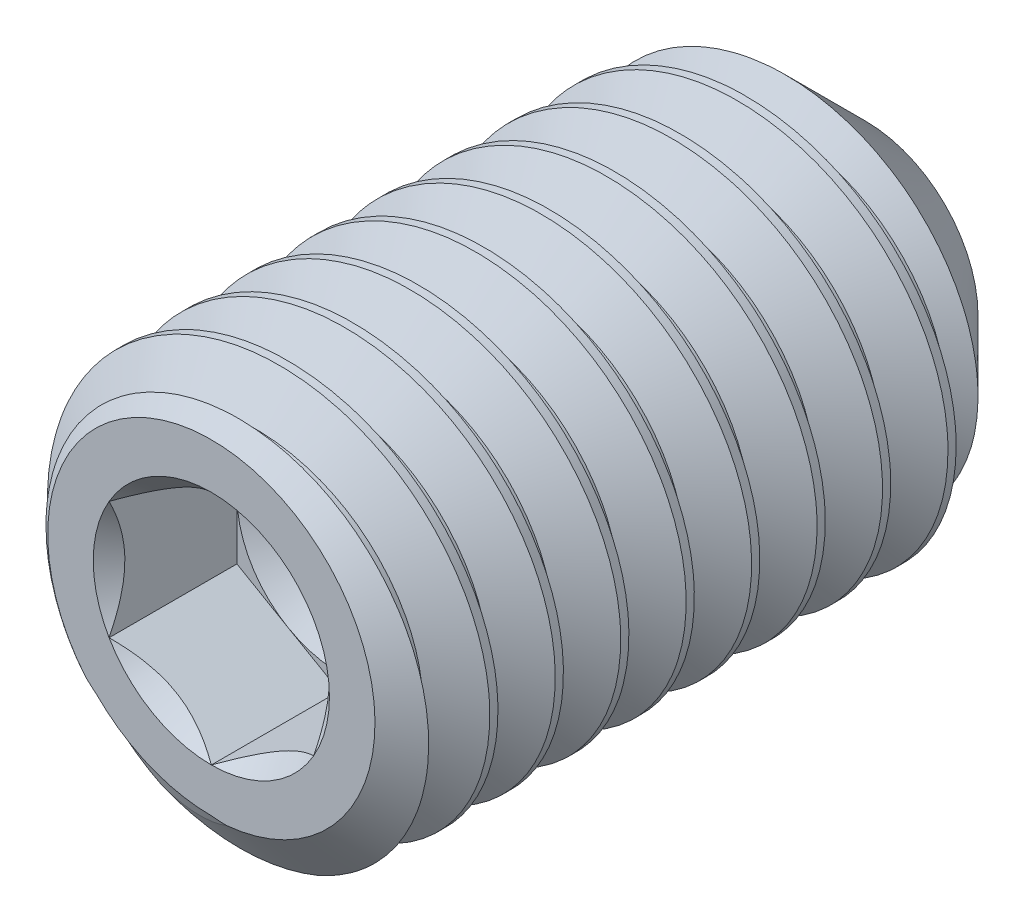
SolidWorks part; units mm, degrees
ref_plane "Front" through (0, 0, 0) normal (0, 0, 1) x (1, 0, 0)
ref_plane "Top" through (0, 0, 0) normal (0, 1, 0) x (1, 0, 0)
ref_plane "Right" through (0, 0, 0) normal (1, 0, 0) x (0, 0, -1)
sketch "Sketch22" plane through (0, 0, 0) normal (1, 0, 0) x (0, 0, -1)
  line L0 (-3.5884, 0) -> (-3.5884, 2)
  line L1 (-3.5884, 2) -> (-3.2383, 2.5)
  line L2 (-3.2383, 2.5) -> (3.2815, 2.5)
  line L3 (3.2815, 2.5) -> (4.4116, 1.3699)
  line L4 (4.4116, 1.3699) -> (3.5884, 0)
  line L5 (3.5884, 0) -> (-3.5884, 0)
  line L6 (3.5884, 0) -> (4.4116, 0) construction
  line L7 (4.4116, 0) -> (4.4116, 1.3699) construction
  line L8 (4.4116, -1.3699) -> (3.5884, 0) construction
  line L9 (-3.2383, -2.5) -> (3.2815, -2.5) construction
  dimension "Dia" = 5
  dimension "Length" = 8
  dimension "D3" = 35
  dimension "D5" = 118
  dimension "D6" = 45
  dimension "D7" = 4
revolve "Revolve1" add sketch "Sketch22" angle 360 about L6
ref_plane "Plane1" through (0, 0, -4.4116) normal (0, 0, 1) x (1, 0, 0)
sketch "Sketch27" plane through (0, 0, -4.4116) normal (0, 0, 1) x (1, 0, 0)
  circle A0 centre (0, 0) radius 2.5 construction
  circle A1 centre (0, 0) radius 2.5
curve "Helix/Spiral1" pitch 0.8 height 8.8 radius 2.5 centre (0, 0, -4.4116) axis (0, 0, 1) start towards (0, 1, 0)
sketch "Sketch28" plane through (0, 0, 0) normal (1, 0, 0) x (0, 0, -1)
  line L0 (4.4116, 2.5) -> (5.1116, 2.5)
  line L1 (5.1116, 2.5) -> (4.8116, 1.9804)
  line L2 (4.8116, 1.9804) -> (4.7116, 1.9804)
  line L3 (4.7116, 1.9804) -> (4.4116, 2.5)
  line L4 (4.5616, 2.2402) -> (4.9616, 2.2402) construction
  line L6 (-3.2383, 2.5) -> (3.2815, 2.5) construction
  dimension "D1" = 0.1
  dimension "D3" = 60
  dimension "D2" = 0.4
sweep "Cut-Sweep2" cut profiles "Sketch28" path "Helix/Spiral1" align with end faces yes
sketch "Sketch23" plane through (0, 0, 3.5884) normal (0, 0, 1) x (1, 0, 0)
  line L1 (0, 1.4434) -> (-1.25, 0.7217)
  line L2 (-1.25, 0.7217) -> (-1.25, -0.7217)
  line L3 (-1.25, -0.7217) -> (0, -1.4434)
  line L4 (0, -1.4434) -> (1.25, -0.7217)
  line L5 (1.25, -0.7217) -> (1.25, 0.7217)
  line L6 (1.25, 0.7217) -> (0, 1.4434)
  circle A0 centre (0, 0) radius 1.25 construction
  dimension "Hex" = 2.5
extrude "Cut-Extrude10" cut sketch "Sketch23" against normal blind 1.5625
sketch "Sketch24" plane through (0, 0, 3.5884) normal (0, 0, 1) x (1, 0, 0)
  circle A0 centre (0, 0) radius 1.4434
extrude "Cut-Extrude11" cut sketch "Sketch24" against normal through all draft 45
sketch "Sketch26" plane through (0, 0, 2.0259) normal (0, 0, 1) x (1, 0, 0)
  circle A0 centre (0, 0) radius 1.25 construction
  circle A1 centre (0, 0) radius 1.25
extrude "Cut-Extrude12" cut sketch "Sketch26" against normal through all draft 60
sketch "Sketch30" plane through (0, 0, 0) normal (1, 0, 0) x (0, 0, -1)
  line L0 (-3.2383, 2.5) -> (3.2815, 2.5) construction
  line L1 (-3.5884, 0) -> (-3.5884, 2) construction
  line L2 (4.4116, 0) -> (4.4116, 1.3699) construction
  line L3 (-3.2383, -2.5) -> (3.2815, -2.5) construction
  point P0 (-3.5884, 2.5)
  point P1 (4.4116, 2.5)
  point P2 (4.4116, -2.5)
  point P11 (3.2116, -2.5)
  dimension "D1" = 1.2
sketch "Sketch31" plane through (0, 0, 0) normal (1, 0, 0) x (0, 0, -1)
  line L2 (3.5884, 0) -> (4.4116, -1.3699)
  line L3 (4.4116, 1.3699) -> (3.5884, 0)
equation "\"D7@Sketch22\"=\"Dia@Sketch22\"*.8"
equation "\"D1@Sketch28\" = \"D4@Helix/Spiral1\" * .125"
equation "\"D2@Sketch28\" = \"D4@Helix/Spiral1\" * .5"
equation "\"D3@Helix/Spiral1\" = \"Length@Sketch22\" + \"D4@Helix/Spiral1\""
equation "\"D1@Sketch30\" = \"D4@Helix/Spiral1\" * 1.5"
equation "\"hex Depth@Cut-Extrude10\" = \"Hex@Sketch23\" * .625"
